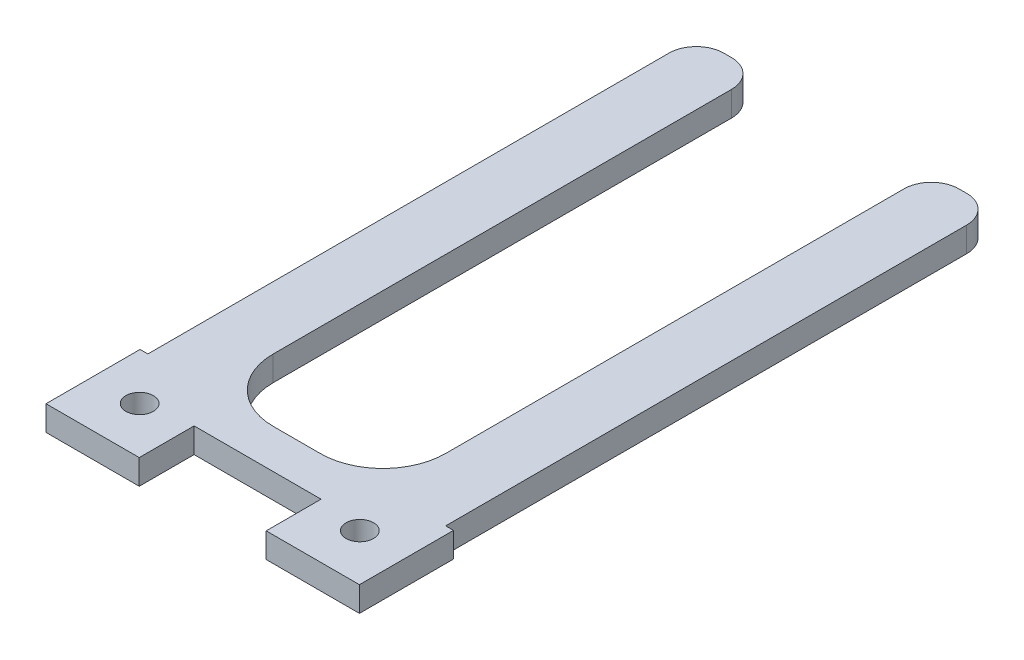
SolidWorks part; units mm, degrees
ref_plane "Alzado" through (0, 0, 0) normal (0, 0, 1) x (1, 0, 0)
ref_plane "Planta" through (0, 0, 0) normal (0, 1, 0) x (1, 0, 0)
ref_plane "Vista lateral" through (0, 0, 0) normal (1, 0, 0) x (0, 0, -1)
sketch "Croquis1" plane through (0, 0, 0) normal (0, 1, 0) x (1, 0, 0)
  line L0 (8.1, 0) -> (-8.1, 0)
  line L1 (-8.1, 0) -> (-8.1, -7)
  line L2 (-8.1, -7) -> (-20, -7)
  line L3 (-20, -7) -> (-20, 5)
  line L4 (-20, 5) -> (-19, 5)
  line L5 (-19, 5) -> (-19, 71.5)
  line L6 (-15.5, 75) -> (-14.5, 75)
  line L7 (-11, 71.5) -> (-11, 5)
  line L8 (-11, 5) -> (11, 5)
  line L9 (0, 5) -> (0, 0)
  line L10 (0, 20.5) -> (0, -26.8333) construction
  line L11 (-20, -1) -> (-8.1, -1) construction
  line L12 (11, 71.5) -> (11, 5)
  line L13 (15.5, 75) -> (14.5, 75)
  line L14 (19, 5) -> (19, 71.5)
  line L15 (20, 5) -> (19, 5)
  line L16 (20, -7) -> (20, 5)
  line L17 (8.1, -7) -> (20, -7)
  line L18 (8.1, 0) -> (8.1, -7)
  circle A0 centre (-14.05, -1) radius 1.75
  circle A1 centre (14.05, -1) radius 1.75
  arc A2 (11, 71.5) -> (14.5, 75) centre (14.5, 71.5) cw
  arc A3 (-14.5, 75) -> (-11, 71.5) centre (-14.5, 71.5) cw
  arc A4 (15.5, 75) -> (19, 71.5) centre (15.5, 71.5) cw
  arc A5 (-19, 71.5) -> (-15.5, 75) centre (-15.5, 71.5) cw
  point P29 (11, 75)
  point P32 (-11, 75)
  point P35 (19, 75)
  point P38 (-19, 75)
  dimension "D8" = 3.5
  dimension "D9" = 3.5
  dimension "D1" = 8
  dimension "D2" = 11.9
  dimension "D3" = 20
  dimension "D4" = 19
  dimension "D5" = 5
  dimension "D6" = 12
  dimension "D7" = 70
extrude "Saliente-Extruir1" add sketch "Croquis1" along normal mid plane 3.175 contours L0 L18 L17 L16 L15 L14 L13 L12 L8 L9 A1 | L9 L8 L7 L6 L5 L4 L3 L2 L1 L0 A0 region at (14.2175, 0, -30.1719) region at (-14.2175, 0, -30.1719)
fillet "Redondeo1" radius 8 2 edges at (11, 0, -5) (-11, 0, -5)
